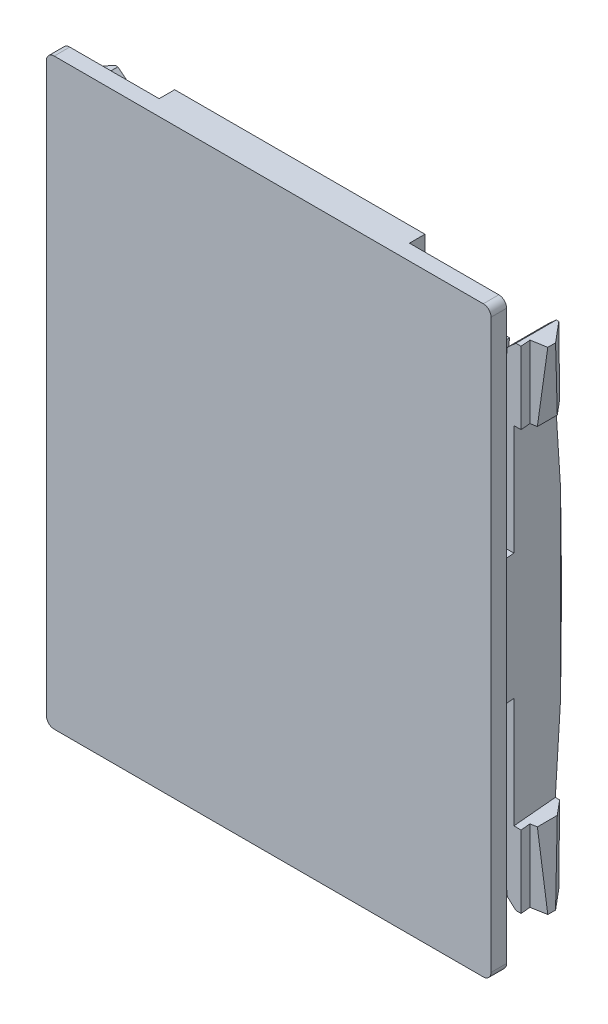
SolidWorks part; units mm, degrees
ref_plane "Front Plane" through (0, 0, 0) normal (0, 0, 1) x (1, 0, 0)
ref_plane "Top Plane" through (0, 0, 0) normal (0, 1, 0) x (1, 0, 0)
ref_plane "Right Plane" through (0, 0, 0) normal (1, 0, 0) x (0, 0, -1)
sketch "Sketch1" plane through (0, 0, 0) normal (0, 0, 1) x (1, 0, 0)
  line L0 (-14.3, 18.25) -> (-14.3, -18.25)
  line L1 (-13.8, -18.75) -> (13.8, -18.75)
  line L2 (14.3, -18.25) -> (14.3, 18.25)
  line L3 (13.8, 18.75) -> (-13.8, 18.75)
  arc A0 (-14.3, -18.25) -> (-13.8, -18.75) centre (-13.8, -18.25) ccw
  arc A1 (13.8, -18.75) -> (14.3, -18.25) centre (13.8, -18.25) ccw
  arc A2 (14.3, 18.25) -> (13.8, 18.75) centre (13.8, 18.25) ccw
  arc A3 (-13.8, 18.75) -> (-14.3, 18.25) centre (-13.8, 18.25) ccw
extrude "Boss-Extrude1" add sketch "Sketch1" along normal blind 2
sketch "Sketch2" plane through (0, 0, 0) normal (0, 0, 1) x (1, 0, 0)
  line L0 (-13.1, 12.5) -> (-10.1, 12.5)
  line L1 (-10.1, 14) -> (-13.1, 14)
  line L2 (-13.1, 14) -> (-13.1, 12.5)
  arc A0 (-10.1, 12.5) -> (-10.1, 14) centre (-10.1, 13.25) ccw
extrude "Boss-Extrude2" add sketch "Sketch2" against normal blind 1.7 and the other way blind 1.7
sketch "Sketch3" plane through (0, 0, 0) normal (0, 0, 1) x (1, 0, 0)
  line L0 (10.1, -14) -> (13.1, -14)
  line L1 (13.1, -14) -> (13.1, -12.5)
  line L2 (13.1, -12.5) -> (10.1, -12.5)
  arc A0 (10.1, -12.5) -> (10.1, -14) centre (10.1, -13.25) ccw
extrude "Boss-Extrude3" add sketch "Sketch3" against normal blind 1.7 and the other way blind 1.7
sketch "Sketch4" plane through (0, 0, 0) normal (0, 0, 1) x (1, 0, 0)
  line L0 (-13.1, -12.5) -> (-13.1, -14)
  line L1 (-13.1, -14) -> (-10.1, -14)
  line L2 (-10.1, -12.5) -> (-13.1, -12.5)
  arc A0 (-10.1, -14) -> (-10.1, -12.5) centre (-10.1, -13.25) ccw
extrude "Boss-Extrude4" add sketch "Sketch4" against normal blind 1.7 and the other way blind 1.7
sketch "Sketch5" plane through (0, 0, 0) normal (0, 0, 1) x (1, 0, 0)
  line L0 (10.1, 12.5) -> (13.1, 12.5)
  line L1 (13.1, 12.5) -> (13.1, 14)
  line L2 (13.1, 14) -> (10.1, 14)
  arc A0 (10.1, 14) -> (10.1, 12.5) centre (10.1, 13.25) ccw
extrude "Boss-Extrude5" add sketch "Sketch5" against normal blind 1.7 and the other way blind 1.7
ref_plane "Plane1" through (0, 0, -3) normal (0, 0, 1) x (1, 0, 0)
sketch "Sketch6" plane through (0, 0, -3) normal (0, 0, 1) x (1, 0, 0)
  line L0 (-19.3, 23.75) -> (-19.3, -23.75)
  line L1 (-19.3, -23.75) -> (19.3, -23.75)
  line L2 (19.3, -23.75) -> (19.3, 23.75)
  line L3 (19.3, 23.75) -> (-19.3, 23.75)
  line L4 (-14.3, -4.045) -> (-11.299, -4.045)
  line L5 (-10.8017, -4.5973) -> (-11.79, -14)
  line L6 (-11.79, -14) -> (-8.55, -14)
  line L7 (-8.05, -14.5) -> (-8.05, -18.75)
  line L8 (-8.05, -18.75) -> (8.05, -18.75)
  line L9 (8.05, -18.75) -> (8.05, -14.5)
  line L10 (8.55, -14) -> (11.79, -14)
  line L11 (11.79, -14) -> (10.8017, -4.5973)
  line L12 (11.299, -4.045) -> (14.3, -4.045)
  line L13 (14.3, -4.045) -> (14.3, 4.045)
  line L14 (14.3, 4.045) -> (11.299, 4.045)
  line L15 (10.8017, 4.5973) -> (11.79, 14)
  line L16 (11.79, 14) -> (8.55, 14)
  line L17 (8.05, 14.5) -> (8.05, 18.75)
  line L18 (8.05, 18.75) -> (-8.05, 18.75)
  line L19 (-8.05, 18.75) -> (-8.05, 14.5)
  line L20 (-8.55, 14) -> (-11.79, 14)
  line L21 (-11.79, 14) -> (-10.8017, 4.5973)
  line L22 (-11.299, 4.045) -> (-14.3, 4.045)
  line L23 (-14.3, 4.045) -> (-14.3, -4.045)
  arc A0 (-11.299, -4.045) -> (-10.8017, -4.5973) centre (-11.299, -4.545) cw
  arc A1 (-8.55, -14) -> (-8.05, -14.5) centre (-8.55, -14.5) cw
  arc A2 (8.05, -14.5) -> (8.55, -14) centre (8.55, -14.5) cw
  arc A3 (10.8017, -4.5973) -> (11.299, -4.045) centre (11.299, -4.545) cw
  arc A4 (11.299, 4.045) -> (10.8017, 4.5973) centre (11.299, 4.545) cw
  arc A5 (8.55, 14) -> (8.05, 14.5) centre (8.55, 14.5) cw
  arc A6 (-8.05, 14.5) -> (-8.55, 14) centre (-8.55, 14.5) cw
  arc A7 (-10.8017, 4.5973) -> (-11.299, 4.045) centre (-11.299, 4.545) cw
extrude "Cut-Extrude1" cut sketch "Sketch6" along normal blind 4
ref_plane "Plane2" through (0, 0, -3.6) normal (0, 0, 1) x (1, 0, 0)
sketch "Sketch7" plane through (0, 0, -3.6) normal (0, 0, 1) x (1, 0, 0)
  line L0 (12.36, -4.0022) -> (13.5477, -15.3027)
  line L1 (13.5477, -15.3027) -> (14.1, -15.8)
  line L2 (14.1, -15.8) -> (15.35, -15.8)
  line L3 (15.35, -15.8) -> (14.7791, -11.15)
  line L4 (14.7791, -11.15) -> (14.04, -11.15)
  line L5 (14.04, -11.15) -> (14.04, 11.15)
  line L6 (14.04, 11.15) -> (14.7791, 11.15)
  line L7 (14.7791, 11.15) -> (15.35, 15.8)
  line L8 (15.35, 15.8) -> (14.1, 15.8)
  line L9 (14.1, 15.8) -> (13.5477, 15.3027)
  line L10 (13.5477, 15.3027) -> (12.36, 4.0022)
  line L11 (12.36, 4.0022) -> (12.36, -4.0022)
extrude "Boss-Extrude6" add sketch "Sketch7" along normal blind 3.8
ref_plane "Plane3" through (0, 0, -3.6) normal (0, 0, 1) x (1, 0, 0)
sketch "Sketch8" plane through (0, 0, -3.6) normal (0, 0, 1) x (1, 0, 0)
  line L0 (-15.35, -15.8) -> (-14.1, -15.8)
  line L1 (-14.1, -15.8) -> (-13.5477, -15.3027)
  line L2 (-13.5477, -15.3027) -> (-12.36, -4.0022)
  line L3 (-12.36, -4.0022) -> (-12.36, 4.0022)
  line L4 (-12.36, 4.0022) -> (-13.5477, 15.3027)
  line L5 (-13.5477, 15.3027) -> (-14.1, 15.8)
  line L6 (-14.1, 15.8) -> (-15.35, 15.8)
  line L7 (-15.35, 15.8) -> (-14.7791, 11.15)
  line L8 (-14.7791, 11.15) -> (-14.04, 11.15)
  line L9 (-14.04, 11.15) -> (-14.04, -11.15)
  line L10 (-14.04, -11.15) -> (-14.7791, -11.15)
  line L11 (-14.7791, -11.15) -> (-15.35, -15.8)
extrude "Boss-Extrude7" add sketch "Sketch8" along normal blind 3.8
sketch "Sketch9" plane through (0, 0, 0) normal (1, 0, 0) x (0, 0, -1)
  line L0 (2.3952, -15.8) -> (8.5, -15.8)
  line L1 (8.5, -15.8) -> (8.5, 15.8)
  line L2 (8.5, 15.8) -> (2.3952, 15.8)
  line L3 (2.3952, 15.8) -> (3.5, 0)
  line L4 (3.5, 0) -> (2.3952, -15.8)
extrude "Cut-Extrude2" cut sketch "Sketch9" along normal blind 20 and the other way blind 20
sketch "Sketch10" plane through (0, 0, 0) normal (0, 1, 0) x (1, 0, 0)
  line L0 (13.6026, 4) -> (14.04, -1)
  line L1 (14.04, -1) -> (14.3, -1)
  line L2 (14.3, -1) -> (14.3, 4)
  line L3 (14.3, 4) -> (13.6026, 4)
extrude "Cut-Extrude3" cut sketch "Sketch10" along normal blind 11.15 and the other way blind 11.15
sketch "Sketch11" plane through (0, 0, 0) normal (0, 1, 0) x (1, 0, 0)
  line L0 (-14.3, 4) -> (-14.3, -1)
  line L1 (-14.3, -1) -> (-14.04, -1)
  line L2 (-14.04, -1) -> (-13.6026, 4)
  line L3 (-13.6026, 4) -> (-14.3, 4)
extrude "Cut-Extrude4" cut sketch "Sketch11" along normal blind 11.15 and the other way blind 11.15
sketch "Sketch12" plane through (0, 0, 0) normal (0, 1, 0) x (1, 0, 0)
  line L0 (12.35, 4.8) -> (12.35, 4.6753)
  line L1 (12.35, 4.6753) -> (15.35, 1.1)
  line L2 (15.35, 1.1) -> (15.35, 0.6)
  line L3 (15.35, 0.6) -> (14.375, 0.4281)
  line L4 (14.375, 0.4281) -> (14.43, -0.2)
  line L5 (14.43, -0.2) -> (17.35, -0.2)
  line L6 (17.35, -0.2) -> (17.35, 4.8)
  line L7 (17.35, 4.8) -> (12.35, 4.8)
extrude "Cut-Extrude5" cut sketch "Sketch12" along normal blind 16 and the other way blind 16
sketch "Sketch13" plane through (0, 0, 0) normal (0, 1, 0) x (1, 0, 0)
  line L0 (-17.35, 4.8) -> (-17.35, -0.2)
  line L1 (-17.35, -0.2) -> (-14.43, -0.2)
  line L2 (-14.43, -0.2) -> (-14.375, 0.4281)
  line L3 (-14.375, 0.4281) -> (-15.35, 0.6)
  line L4 (-15.35, 0.6) -> (-15.35, 1.1)
  line L5 (-15.35, 1.1) -> (-12.35, 4.6753)
  line L6 (-12.35, 4.6753) -> (-12.35, 4.8)
  line L7 (-12.35, 4.8) -> (-17.35, 4.8)
extrude "Cut-Extrude6" cut sketch "Sketch13" along normal blind 16 and the other way blind 16
ref_plane "Plane4" through (0, 0, 2) normal (0, 0, 1) x (1, 0, 0)
ref_plane "ABDECK XY" through (0, 0, 2) normal (0, 0, 1) x (1, 0, 0)
ref_plane "ABDECK XZ" through (0, 0, 0) normal (0, -1, 0) x (-1, 0, 0)
ref_plane "ABDECK YZ" through (0, 0, 0) normal (1, 0, 0) x (0, 0, -1)
ref_axis "ABDECK X" through (-80.9, 0, 2) along (1, 0, 0)
ref_axis "ABDECK Y" through (0, -50, 2) along (0, 1, 0)
ref_axis "ABDECK Z" through (0, 0, 80.9) along (0, 0, -1)
sketch3d "ABDECK"
  point P0 (0, 0, 2)
